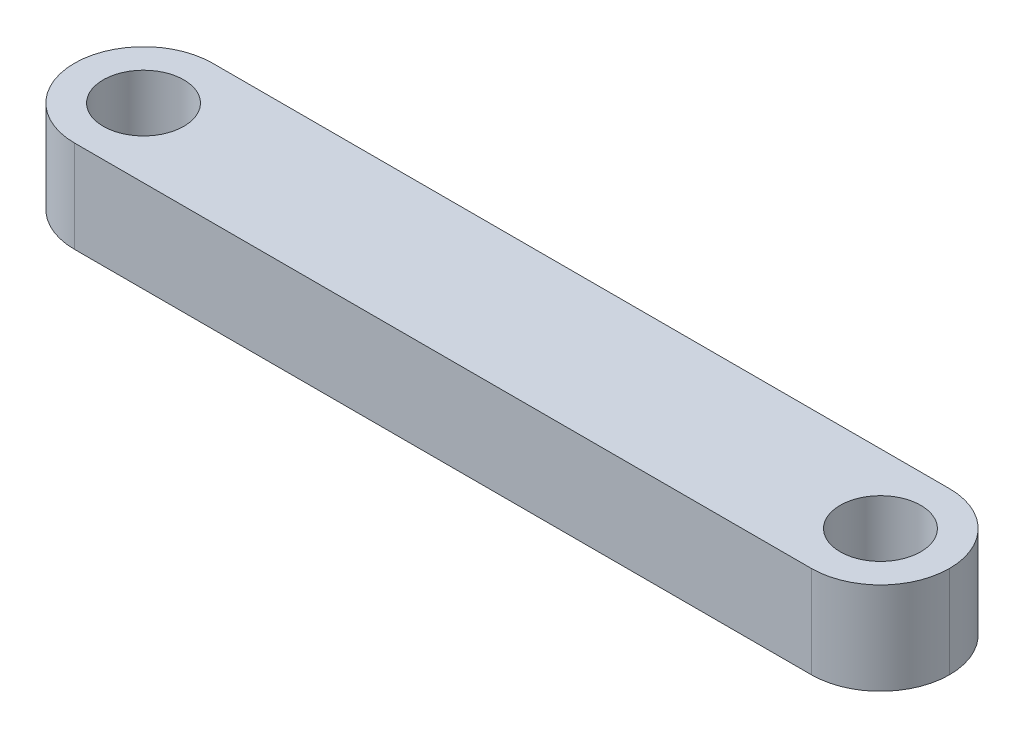
SolidWorks part; units mm, degrees
ref_plane "Alzado" through (0, 0, 0) normal (0, 0, 1) x (1, 0, 0)
ref_plane "Planta" through (0, 0, 0) normal (0, 1, 0) x (1, 0, 0)
ref_plane "Vista lateral" through (0, 0, 0) normal (1, 0, 0) x (0, 0, -1)
sketch "Croquis1" plane through (0, 0, 0) normal (0, 1, 0) x (1, 0, 0)
  line L0 (0, 3) -> (38, 3) construction
  line L1 (0, 0) -> (38, 0)
  line L2 (0, 0) -> (0, 6)
  line L3 (0, 6) -> (38, 6)
  line L4 (38, 0) -> (38, 6)
  circle A0 centre (3, 3) radius 1.75
  circle A1 centre (35, 3) radius 1.75
  dimension "D1" = 3.5
  dimension "D2" = 3.5
  dimension "D3" = 3
  dimension "D4" = 3
  dimension "D5" = 32
  dimension "D6" = 6
extrude "Saliente-Extruir1" add sketch "Croquis1" along normal blind 4
fillet "Redondeo1" radius 3 4 edges at (38, 2, -6) (38, 2, 0) (0, 2, -6) (0, 2, 0)
